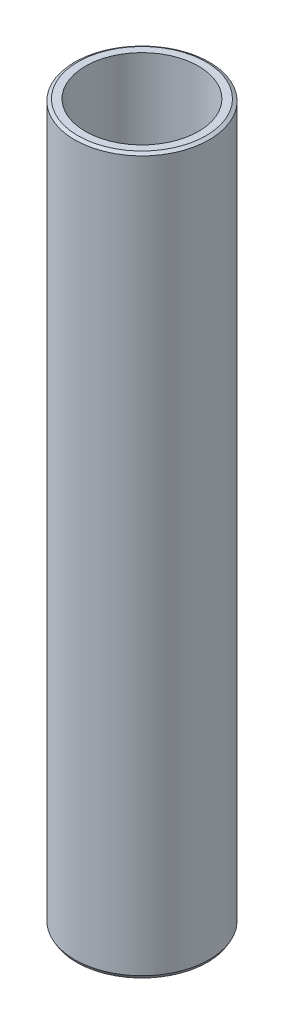
SolidWorks part; units mm, degrees
ref_plane "Front Plane" through (0, 0, 0) normal (0, 0, 1) x (1, 0, 0)
ref_plane "Top Plane" through (0, 0, 0) normal (0, 1, 0) x (1, 0, 0)
ref_plane "Right Plane" through (0, 0, 0) normal (1, 0, 0) x (0, 0, -1)
sketch "Sketch1" plane through (0, 0, 0) normal (0, 1, 0) x (1, 0, 0)
  circle A0 centre (0, 0) radius 45
  dimension "SHAFT_OD" = 90
extrude "Boss-Extrude1" add sketch "Sketch1" along normal blind 478.0721
sketch "Sketch2" plane through (0, 0, 0) normal (0, 1, 0) x (1, 0, 0)
  circle A0 centre (0, 0) radius 37.8106
  dimension "BORE_D" = 75.6211
extrude "Cut-Extrude1" cut sketch "Sketch2" along normal through all
chamfer "Chamfer1" distance 1.2665 angle 60 2 edges at (0, 478.0721, 45) (0, 0, 45) first distance on face at (0, 478.0721, 45) first distance on face at (0, 0, 37.8106)
